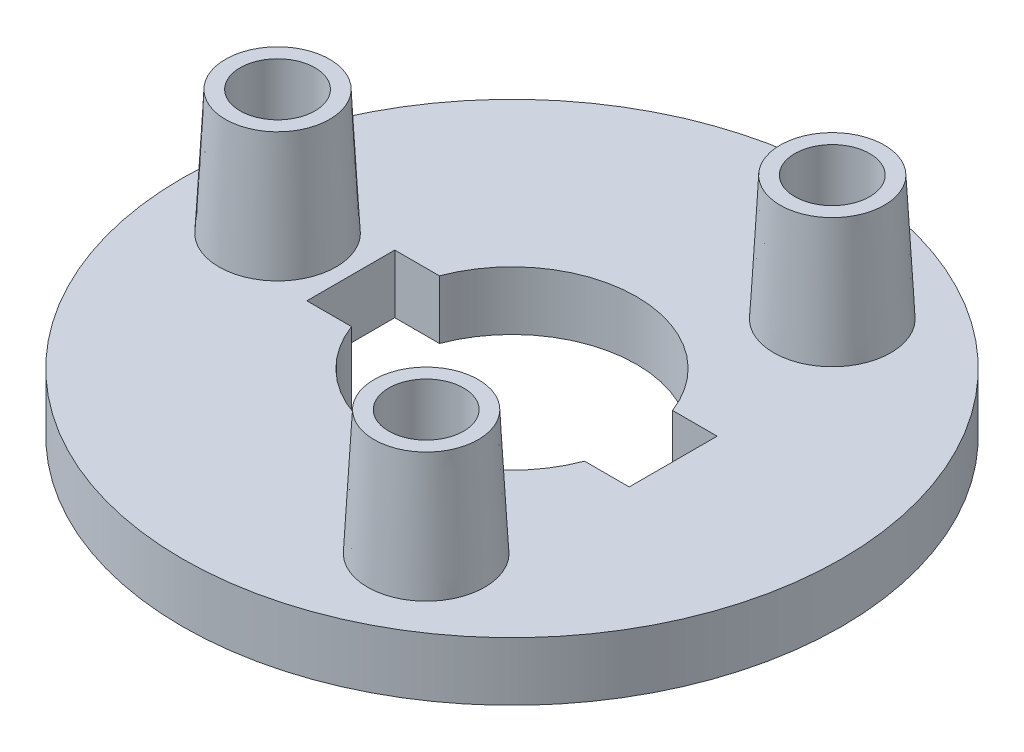
SolidWorks part; units mm, degrees
ref_plane "Plan de face" through (0, 0, 0) normal (0, 0, 1) x (1, 0, 0)
ref_plane "Plan de dessus" through (0, 0, 0) normal (0, 1, 0) x (1, 0, 0)
ref_plane "Plan de droite" through (0, 0, 0) normal (1, 0, 0) x (0, 0, -1)
sketch "Esquisse1" plane through (0, 0, 0) normal (0, 1, 0) x (1, 0, 0)
  circle A0 centre (0, 0) radius 22.5
  dimension "D1" = 45
extrude "Boss.-Extru.1" add sketch "Esquisse1" along normal blind 4
sketch "Esquisse2" plane through (0, 4, 0) normal (0, 1, 0) x (1, 0, 0)
  circle A0 centre (-16, 0) radius 4
  dimension "D2" = 8
  dimension "D1" = 16
extrude "Boss.-Extru.3" add sketch "Esquisse2" along normal blind 8.5
chamfer "Chanfrein1" distance 8.5 angle 3 1 edges at (-16, 12.5, 4)
sketch "Esquisse4" plane through (0, 12.5, 0) normal (0, 1, 0) x (1, 0, 0)
  circle A0 centre (-16, 0) radius 2.5545
  circle A1 centre (-16, 0) radius 3.5545 construction
  dimension "D1" = 0
  dimension "D2" = 1
  dimension "D3" = 5.1091
extrude "Enlèv. mat.-Extru.1" cut sketch "Esquisse4" along direction (0, 1, 0) on the side against the normal through all
pattern_circular "Répétition circulaire1" count 3 over 360 about axis through (0, 0, 0) along (0, 1, 0) of "Boss.-Extru.3", "Chanfrein1", "Enlèv. mat.-Extru.1"
sketch "Esquisse5" plane through (0, 4, 0) normal (0, 1, 0) x (1, 0, 0)
  circle A0 centre (0, 0) radius 8.5
  dimension "D1" = 17
extrude "Enlèv. mat.-Extru.2" cut sketch "Esquisse5" against normal up to next
sketch "Esquisse6" plane through (0, 4, 0) normal (0, 1, 0) x (1, 0, 0)
  line L1 (-11, 3) -> (11, 3)
  line L2 (-11, 3) -> (-11, -3)
  line L3 (-11, -3) -> (11, -3)
  line L4 (11, 3) -> (11, -3)
  dimension "D1" = 3
  dimension "D2" = 3
  dimension "D3" = 11
  dimension "D4" = 11
extrude "Enlèv. mat.-Extru.4" cut sketch "Esquisse6" against normal up to next contours L1 L4 L3 L2
sketch "Esquisse7" plane through (0, 0, 0) normal (0, 1, 0) x (1, 0, 0)
  line L0 (-7.953, -3) -> (-11, -3)
  line L1 (-8.01, -8.3212) -> (-5.8948, -6.1238)
  arc A0 (-11, -3) -> (-8.01, -8.3212) centre (-4.77, -3) ccw
  arc A1 (-7.953, -3) -> (7.953, -3) centre (0, 0) ccw construction
  arc A2 (-5.8948, -6.1238) -> (-7.953, -3) centre (0, 0) cw
  dimension "D1" = 3.05
extrude "Boss.-Extru.5" add sketch "Esquisse7" against normal blind 8
sketch "Esquisse8" plane through (0, 0, 0) normal (0.7204, 0, 0.6935) x (0.6935, 0, -0.7204)
  line L0 (-11.55, -8) -> (-11.55, 0) construction
  line L1 (-8.5, -8) -> (-11.55, -8)
  line L2 (-8.5, -8) -> (-8.5, -5)
  line L3 (-8.5, -5) -> (-11.55, -5)
  line L4 (-11.55, -8) -> (-11.55, -5)
  dimension "D1" = 3
extrude "Boss.-Extru.6" add sketch "Esquisse8" along normal blind 5 contours L3 L4 L1 L2
pattern_circular "Répétition circulaire3" count 2 over 360 about axis through (0, 0, 0) along (0, 1, 0) of "Boss.-Extru.5", "Boss.-Extru.6"
